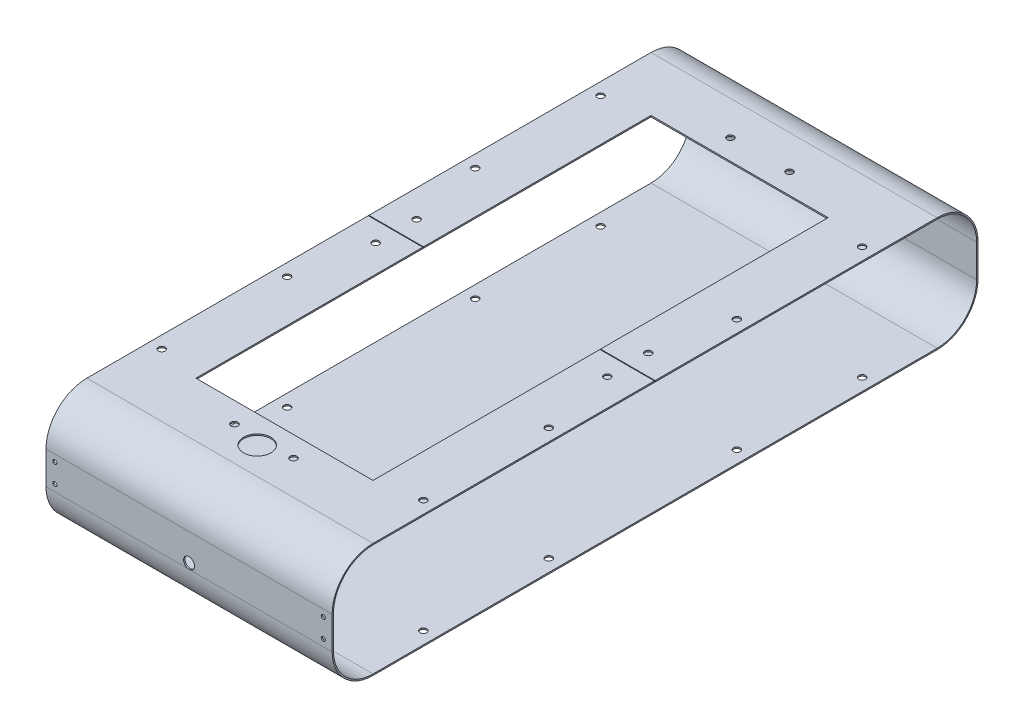
SolidWorks part; units mm, degrees
material "3.0205 (EN-AW 1200)"
ref_plane "Alzado" through (0, 0, 0) normal (0, 0, 1) x (1, 0, 0)
ref_plane "Planta" through (0, 0, 0) normal (0, 1, 0) x (1, 0, 0)
ref_plane "Vista lateral" through (0, 0, 0) normal (1, 0, 0) x (0, 0, -1)
sketch "Croquis1" plane through (0, 0, 0) normal (1, 0, 0) x (0, 0, -1)
  line L1 (207, -42) -> (-207, -42)
  line L2 (237, -12) -> (237, 12)
  line L3 (207, 42) -> (-207, 42)
  line L4 (-237, -12) -> (-237, 12)
  line L5 (237, -42) -> (-237, 42) construction
  line L6 (237, 42) -> (-237, -42) construction
  arc A4 (-237, 12) -> (-207, 42) centre (-207, 12) cw
  arc A5 (207, -42) -> (237, -12) centre (207, -12) ccw
  arc A6 (207, 42) -> (237, 12) centre (207, 12) cw
  arc A7 (-237, -12) -> (-207, -42) centre (-207, -12) ccw
  point P0 (0, 0)
  dimension "D4" = 30
  dimension "D5" = 30
  dimension "D1" = 474
  dimension "D2" = 84
extrude "Saliente-Extruir1" add sketch "Croquis1" along normal mid plane 220
shell "Vaciado2" thickness 1 removed face at (110, 0, 0)
sketch "Croquis2" plane through (110, 0, 0) normal (1, 0, 0) x (0, 0, -1)
  line L8 (237, -12) -> (237, 12)
  line L9 (207, 42) -> (-207, 42)
  line L10 (-237, 12) -> (-237, -12)
  line L11 (-207, -42) -> (207, -42)
  line L12 (237, -12) -> (237, 12)
  line L13 (207, 42) -> (-207, 42)
  line L14 (-237, 12) -> (-237, -12)
  line L15 (-207, -42) -> (207, -42)
  arc A8 (207, -42) -> (237, -12) centre (207, -12) ccw
  arc A9 (237, 12) -> (207, 42) centre (207, 12) ccw
  arc A10 (-207, 42) -> (-237, 12) centre (-207, 12) ccw
  arc A11 (-237, -12) -> (-207, -42) centre (-207, -12) ccw
  arc A12 (207, -42) -> (237, -12) centre (207, -12) ccw
  arc A13 (237, 12) -> (207, 42) centre (207, 12) ccw
  arc A14 (-207, 42) -> (-237, 12) centre (-207, 12) ccw
  arc A15 (-237, -12) -> (-207, -42) centre (-207, -12) ccw
  dimension "D1" = 0
sketch "Croquis5" plane through (0, 0, 0) normal (1, 0, 0) x (0, 0, -1)
  line L27 (-237, 12) -> (-237, -12)
  line L28 (-207, -42) -> (207, -42)
  line L29 (237, -12) -> (237, 12)
  line L30 (207, 42) -> (-207, 42)
  line L31 (-237, 12) -> (-237, -12)
  line L32 (-207, -42) -> (207, -42)
  line L33 (237, -12) -> (237, 12)
  line L34 (207, 42) -> (-207, 42)
  arc A31 (-237, -12) -> (-207, -42) centre (-207, -12) ccw
  arc A32 (207, -42) -> (237, -12) centre (207, -12) ccw
  arc A33 (237, 12) -> (207, 42) centre (207, 12) ccw
  arc A34 (-207, 42) -> (-237, 12) centre (-207, 12) ccw
  arc A35 (-237, -12) -> (-207, -42) centre (-207, -12) ccw
  arc A36 (207, -42) -> (237, -12) centre (207, -12) ccw
  arc A37 (237, 12) -> (207, 42) centre (207, 12) ccw
  arc A38 (-207, 42) -> (-237, 12) centre (-207, 12) ccw
  dimension "D1" = 0
sketch "Croquis6" plane through (-110, 0, 0) normal (-1, 0, 0) x (0, 0, 1)
  line L8 (207, 42) -> (-207, 42)
  line L9 (237, -12) -> (237, 12)
  line L10 (-207, -42) -> (207, -42)
  line L11 (-237, 12) -> (-237, -12)
  line L12 (207, 42) -> (-207, 42)
  line L13 (237, -12) -> (237, 12)
  line L14 (-207, -42) -> (207, -42)
  line L15 (-237, 12) -> (-237, -12)
  arc A8 (237, 12) -> (207, 42) centre (207, 12) ccw
  arc A9 (207, -42) -> (237, -12) centre (207, -12) ccw
  arc A10 (-237, -12) -> (-207, -42) centre (-207, -12) ccw
  arc A11 (-207, 42) -> (-237, 12) centre (-207, 12) ccw
  arc A12 (237, 12) -> (207, 42) centre (207, 12) ccw
  arc A13 (207, -42) -> (237, -12) centre (207, -12) ccw
  arc A14 (-237, -12) -> (-207, -42) centre (-207, -12) ccw
  arc A15 (-207, 42) -> (-237, 12) centre (-207, 12) ccw
  dimension "D1" = 0
extrude "Cortar-Extruir1" cut sketch "Croquis6" against normal blind 10
sketch "Croquis7" plane through (0, 0, 237) normal (0, 0, 1) x (1, 0, 0)
  line L0 (82.1341, 15) -> (-72.1341, 15)
  line L1 (-72.1341, -15) -> (82.1341, -15)
  line L2 (-72.1341, 15) -> (82.1341, -15) construction
  line L3 (82.1341, 15) -> (-72.1341, -15) construction
  line L4 (110, 12) -> (-100, -12) construction
  arc A0 (-74.8961, 14.1673) -> (-74.8961, -14.1673) centre (-65.5, 0) ccw
  arc A1 (84.8961, -14.1673) -> (84.8961, 14.1673) centre (75.5, 0) ccw
  spline S0 degree 2 poles (-72.1341, 15) (-72.8713, 15) (-73.5765, 14.7873) (-74.2822, 14.5745) (-74.8961, 14.1673) knots 0 0 0 0.5 0.5 1 1 1
  spline S1 degree 2 poles (-74.8961, -14.1673) (-74.2818, -14.5748) (-73.5765, -14.7873) (-72.8707, -15) (-72.1341, -15) knots 0 0 0 0.5 0.5 1 1 1
  spline S2 degree 2 poles (82.1341, -15) (82.8713, -15) (83.5765, -14.7873) (84.2822, -14.5745) (84.8961, -14.1673) knots 0 0 0 0.5 0.5 1 1 1
  spline S3 degree 2 poles (84.8961, 14.1673) (84.2818, 14.5748) (83.5765, 14.7873) (82.8707, 15) (82.1341, 15) knots 0 0 0 0.5 0.5 1 1 1
  point P16 (5, 0)
  point P17 (5, 0)
sketch "Croquis8" plane through (0, 0, 237) normal (0, 0, 1) x (1, 0, 0)
  line L0 (110, 12) -> (103.5, 12) construction
  line L1 (110, 12) -> (-100, 12) construction
  line L2 (103.5, 12) -> (103.5, 7) construction
  line L3 (110, -12) -> (103.5, -12) construction
  line L4 (110, -12) -> (-100, -12) construction
  line L5 (103.5, -12) -> (103.5, -7) construction
  line L6 (5, 0) -> (5, 71.8665) construction
  line L7 (-72.1341, 15) -> (82.1341, -15) construction
  circle A0 centre (103.5, 7) radius 1.5
  circle A1 centre (103.5, -7) radius 1.5
  circle A2 centre (-93.5, -7) radius 1.5
  circle A3 centre (-93.5, 7) radius 1.5
  dimension "D3" = 3
  dimension "D6" = 3
  dimension "D1" = 6.5
  dimension "D2" = 5
  dimension "D4" = 6.5
  dimension "D5" = 5
extrude "Cortar-Extruir4" cut sketch "Croquis8" against normal blind 5
sketch "Croquis9" plane through (0, 0, 237) normal (0, 0, 1) x (1, 0, 0)
  line L0 (5, -12) -> (5, -4) construction
  line L1 (110, -12) -> (-100, -12) construction
  circle A0 centre (5, -8) radius 4
  dimension "D1" = 8
extrude "Cortar-Extruir5" cut sketch "Croquis9" against normal blind 5
sketch "Croquis10" plane through (0, 42, 0) normal (0, 1, 0) x (1, 0, 0)
  line L0 (110, 207) -> (101, 207) construction
  line L1 (110, 207) -> (-100, 207) construction
  line L2 (101, 207) -> (101, 161.01) construction
  line L3 (101, 161.01) -> (101, 69.01) construction
  line L4 (5, 207) -> (5, -207) construction
  line L5 (110, -207) -> (-100, -207) construction
  line L6 (5, 0) -> (-100, 0) construction
  line L7 (-100, -207) -> (-100, 207) construction
  line L8 (-91, 161.01) -> (-91, 69.01) construction
  line L9 (-91, 207) -> (-91, 161.01) construction
  line L10 (101, -161.01) -> (101, -69.01) construction
  line L11 (101, -207) -> (101, -161.01) construction
  line L12 (-91, -161.01) -> (-91, -69.01) construction
  circle A0 centre (101, 161.01) radius 2.5
  circle A1 centre (101, 69.01) radius 2.5
  circle A2 centre (-91, 69.01) radius 2.5
  circle A3 centre (-91, 161.01) radius 2.5
  circle A4 centre (101, -69.01) radius 2.5
  circle A5 centre (101, -161.01) radius 2.5
  circle A6 centre (-91, -161.01) radius 2.5
  circle A7 centre (-91, -69.01) radius 2.5
  dimension "D3" = 5
  dimension "D5" = 5
  dimension "D1" = 9
  dimension "D2" = 45.99
  dimension "D4" = 92
extrude "Cortar-Extruir6" cut sketch "Croquis10" against normal through all
sketch "Croquis11" plane through (0, 42, 0) normal (0, 1, 0) x (1, 0, 0)
  line L8 (-60, 167) -> (-60, -167)
  line L9 (-60, -167) -> (70, -167)
  line L10 (70, -167) -> (70, 167)
  line L11 (70, 167) -> (-60, 167)
  line L12 (-60, 167) -> (-60, -167)
  line L13 (-60, -167) -> (70, -167)
  line L14 (70, -167) -> (70, 167)
  line L15 (70, 167) -> (-60, 167)
  dimension "D1" = 40
extrude "Cortar-Extruir7" cut sketch "Croquis11" against normal blind 8
sketch "Croquis12" plane through (0, 42, 0) normal (0, 1, 0) x (1, 0, 0)
  line L0 (70, 167) -> (-60, 167) construction
  line L1 (-60, 167) -> (-16.6667, 167) construction
  line L2 (-16.6667, 167) -> (26.6667, 167) construction
  line L3 (26.6667, 167) -> (70, 167) construction
  line L4 (-16.6667, 167) -> (-16.6667, 182) construction
  line L5 (26.6667, 167) -> (26.6667, 182) construction
  line L6 (0, 0) -> (160.0626, 0) construction
  circle A0 centre (-16.6667, 182) radius 2.5
  circle A1 centre (26.6667, 182) radius 2.5
  circle A2 centre (26.6667, -182) radius 2.5
  circle A3 centre (-16.6667, -182) radius 2.5
  point P15 (-16.6667, -182)
  point P16 (26.6667, -182)
  dimension "D5" = 5
  dimension "D6" = 5
  dimension "D1" = 43.3333
  dimension "D2" = 43.3333
  dimension "D3" = 15
  dimension "D4" = 15
extrude "Cortar-Extruir8" cut sketch "Croquis12" against normal blind 8
sketch "Croquis13" plane through (0, 42, 0) normal (0, 1, 0) x (1, 0, 0)
  line L0 (0, 0) -> (-100, 0) construction
  line L1 (-100, -207) -> (-100, 207) construction
  line L2 (-60, 167) -> (-60, -167) construction
  line L3 (-100, 0) -> (-60, 0)
  line L4 (-100, 0) -> (-100, -0.5)
  line L5 (-100, -0.5) -> (-60, -0.5)
  line L6 (-60, 0) -> (-60, -0.5)
  line L7 (0, 0) -> (0, 83.4895) construction
  line L8 (5, 167) -> (5, -79.8783) construction
  line L9 (70, 167) -> (-60, 167) construction
  line L10 (10, 0) -> (110, 0) construction
  line L11 (70, 0) -> (70, -0.5)
  line L12 (110, -0.5) -> (70, -0.5)
  line L13 (110, 0) -> (110, -0.5)
  line L14 (110, 0) -> (70, 0)
  dimension "D1" = 0.5
extrude "Cortar-Extruir9" cut sketch "Croquis13" against normal blind 1
sketch "Croquis14" plane through (0, 42, 0) normal (0, 1, 0) x (1, 0, 0)
  line L0 (90, 0) -> (90, 15) construction
  line L1 (110, 0) -> (70, 0) construction
  line L2 (90, 0) -> (90, -15) construction
  line L3 (5, 167) -> (5, -69.3269) construction
  line L4 (70, 167) -> (-60, 167) construction
  line L5 (-80, 0) -> (-80, -15) construction
  line L6 (-80, 0) -> (-80, 15) construction
  circle A0 centre (90, 15) radius 2.5
  circle A1 centre (90, -15) radius 2.5
  circle A2 centre (-80, -15) radius 2.5
  circle A3 centre (-80, 15) radius 2.5
  dimension "D3" = 5
  dimension "D4" = 5
  dimension "D1" = 15
  dimension "D2" = 15
extrude "Cortar-Extruir10" cut sketch "Croquis14" against normal blind 1
sketch "Croquis15" plane through (0, 42, 0) normal (0, 1, 0) x (1, 0, 0)
  line L0 (5, 167) -> (5, -167) construction
  line L1 (70, 167) -> (-60, 167) construction
  line L2 (-60, -167) -> (70, -167) construction
ref_plane "Plano1" through (5, 0, 0) normal (1, 0, 0) x (0, 0, -1)
sketch "Croquis16" plane through (0, 42, 0) normal (0, 1, 0) x (1, 0, 0)
  line L0 (-60, -167) -> (70, -167) construction
  circle A0 centre (5, -187) radius 10
  dimension "D1" = 20
  dimension "D2" = 20
extrude "Cortar-Extruir11" cut sketch "Croquis16" against normal blind 10
